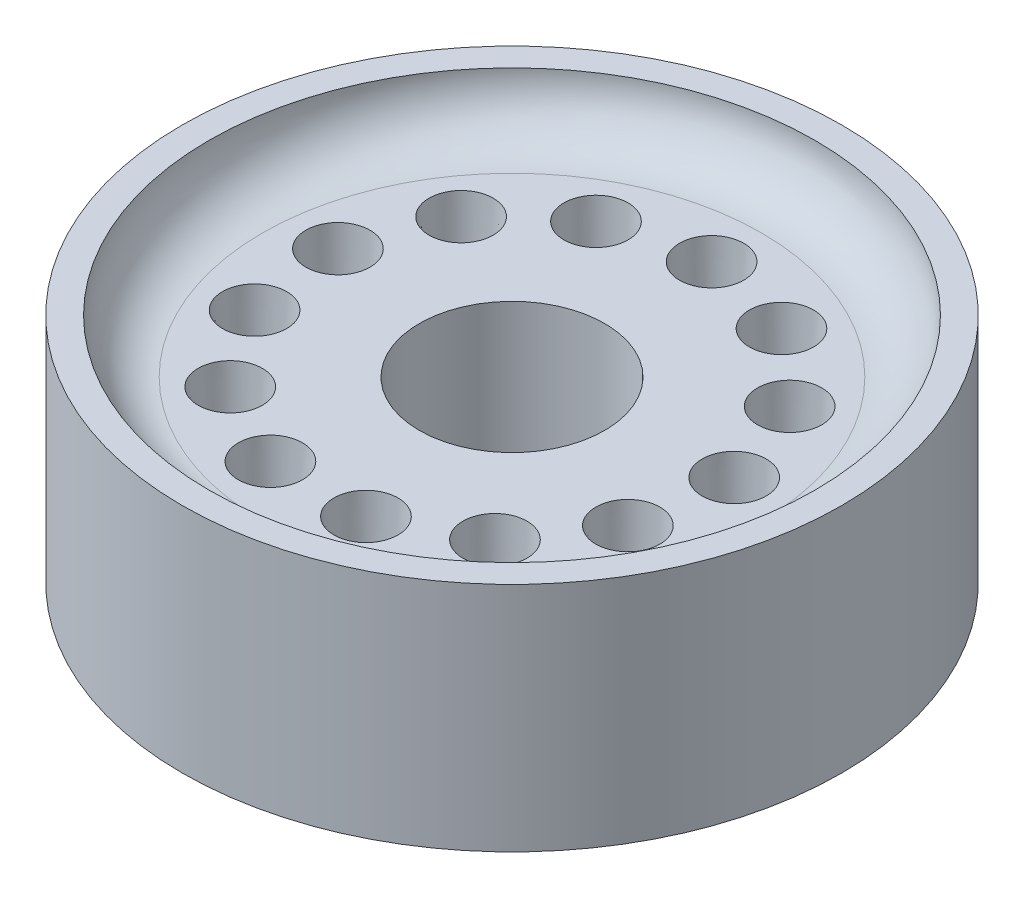
SolidWorks part; units mm, degrees
ref_plane "Plan de face" through (0, 0, 0) normal (0, 0, 1) x (1, 0, 0)
ref_plane "Plan de dessus" through (0, 0, 0) normal (0, 1, 0) x (1, 0, 0)
ref_plane "Plan de droite" through (0, 0, 0) normal (1, 0, 0) x (0, 0, -1)
sketch "Esquisse1" plane through (0, 0, 0) normal (0, 1, 0) x (1, 0, 0)
  arc A0 (-4.625, -8.0107) -> (4.625, -8.0107) centre (0, 0) ccw
  arc A3 (4.625, 8.0107) -> (-4.625, 8.0107) centre (0, 0) ccw
  arc A4 (-4.625, -8.0107) -> (-4.625, 8.0107) centre (0, 0) cw
  arc A5 (4.625, -8.0107) -> (4.625, 8.0107) centre (0, 0) ccw
  dimension "D1" = 18.5
extrude "Boss.-Extru.1" add sketch "Esquisse1" along normal blind 6.5 contours A0 A5 A3 A4
sketch "Esquisse6" plane through (0, 6.5, 0) normal (0, 1, 0) x (1, 0, 0)
  circle A0 centre (0, 0) radius 2.6
  dimension "D1" = 5.2
extrude "Enlèv. mat.-Extru.2" cut sketch "Esquisse6" against normal through all contours A0
sketch "Esquisse7" plane through (0, 6.5, 0) normal (0, 1, 0) x (1, 0, 0)
  circle A0 centre (0, 0) radius 8.5
  dimension "D1" = 17
extrude "Enlèv. mat.-Extru.4" cut sketch "Esquisse7" against normal blind 1.5
fillet "Congé1" radius 1.5 1 edges at (0, 5, 8.5)
sketch "Esquisse3" plane through (0, 5, 0) normal (0, 1, 0) x (1, 0, 0)
  circle A0 centre (0, 5.6) radius 0.9
  circle A1 centre (2.6024, 4.9586) radius 0.9
  circle A2 centre (4.6087, 3.1812) radius 0.9
  circle A3 centre (5.5592, 0.675) radius 0.9
  circle A4 centre (5.2361, -1.9858) radius 0.9
  circle A5 centre (3.7135, -4.1917) radius 0.9
  circle A6 centre (1.3402, -5.4373) radius 0.9
  circle A7 centre (-1.3402, -5.4373) radius 0.9
  circle A8 centre (-3.7135, -4.1917) radius 0.9
  circle A9 centre (-5.2361, -1.9858) radius 0.9
  circle A10 centre (-5.5592, 0.675) radius 0.9
  circle A11 centre (-4.6087, 3.1812) radius 0.9
  circle A12 centre (-2.6024, 4.9586) radius 0.9
  point P29 (0, 0)
  dimension "D1" = 1.8
  dimension "D2" = 5.6
  dimension "D3" = 13
extrude "Enlèv. mat.-Extru.3" cut sketch "Esquisse3" against normal through all draft 4
